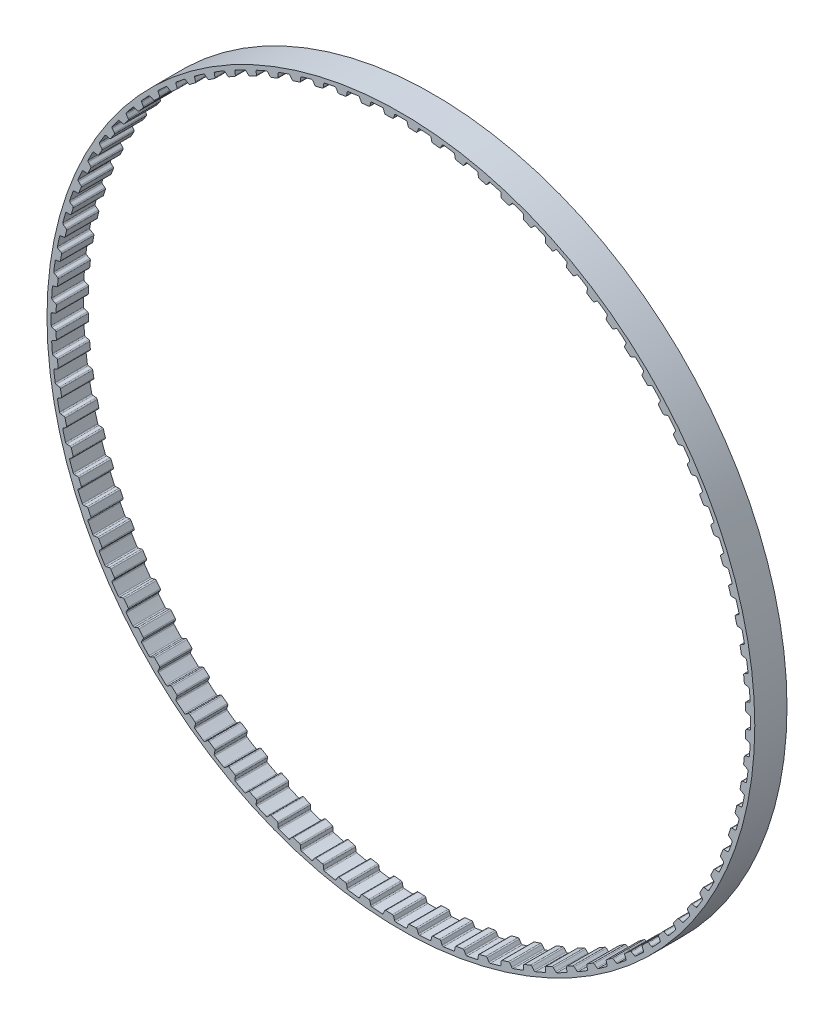
SolidWorks part; units mm, degrees
ref_plane "Front Plane" through (0, 0, 0) normal (0, 0, 1) x (1, 0, 0)
ref_plane "Top Plane" through (0, 0, 0) normal (0, 1, 0) x (1, 0, 0)
ref_plane "Right Plane" through (0, 0, 0) normal (1, 0, 0) x (0, 0, -1)
sketch "Sketch1" plane through (0, 0, 0) normal (0, 0, 1) x (1, 0, 0)
  line L0 (0, 0) -> (-4.6402, 135.8324) construction
  line L1 (0, 0) -> (4.6402, 135.8324) construction
  line L2 (4.6402, 135.8324) -> (-4.6402, 135.8324) construction
  line L3 (4.6402, 135.8324) -> (-4.6402, 135.8324) construction
  circle A0 centre (0, 0) radius 139.4676
  circle A1 centre (0, 0) radius 135.9116
  circle A2 centre (0, 0) radius 137.8166 construction
  dimension "OD" = 278.9352
  dimension "Angle Distance" = 3.913
  dimension "hs" = 3.556
  dimension "ht" = 1.905
extrude "Boss-Extrude1" add sketch "Sketch1" along normal mid plane 12.7
sketch "Sketch2" plane through (0, 0, 0) normal (0, 0, 1) x (1, 0, 0)
  line L1 (0, 139.4676) -> (0, 0) construction
  line L2 (-4.7625, 136.8422) -> (4.7625, 136.8422) construction
  line L4 (-3.0019, 135.8883) -> (-6.2785, 135.7764)
  line L5 (-3.0019, 135.8883) -> (-2.3804, 137.796)
  line L6 (-6.2785, 135.7764) -> (-7.0286, 137.6372)
  line L7 (0, 0) -> (-4.6402, 135.8324) construction
  line L8 (-2.3804, 137.796) -> (-7.0286, 137.6372) construction
  line L9 (2.3804, 137.796) -> (7.0286, 137.6372) construction
  line L10 (6.2785, 135.7764) -> (7.0286, 137.6372)
  line L11 (3.0019, 135.8883) -> (2.3804, 137.796)
  line L12 (3.0019, 135.8883) -> (6.2785, 135.7764)
  line L13 (0, 0) -> (53.3719, 128.8513) construction
  line L14 (-4.7625, 136.8422) -> (-14.2645, 136.18) construction
  line L15 (-9.5135, 136.5111) -> (0, 0) construction
  line L16 (-14.2645, 136.18) -> (-14.1589, 135.1721) construction
  circle A0 centre (0, 0) radius 137.8166 construction
  circle A1 centre (0, 0) radius 137.8166
  circle A2 centre (0, 0) radius 136.8422 construction
  circle A4 centre (0, 0) radius 139.4676 construction
  circle A5 centre (0, 0) radius 135.9116 construction
  point P16 (-2.6912, 136.8422)
  point P20 (0, 136.8422)
  dimension "D1" = 22.5
  dimension "bt" = 4.6482
  dimension "b" = 40
  dimension "Pitch" = 9.525
sketch "Sketch3" plane through (0, 0, 0) normal (0, 0, 1) x (1, 0, 0)
  line L0 (-3.3641, 135.87) -> (3.3641, 135.87)
  line L2 (-3.0019, 135.8883) -> (-2.3804, 137.796) construction
  line L3 (3.0019, 135.8883) -> (2.3804, 137.796) construction
  line L5 (-2.8937, 136.2204) -> (-2.4928, 137.4512)
  line L7 (2.8937, 136.2204) -> (2.4928, 137.4512)
  arc A0 (2.8937, 136.2204) -> (3.3641, 135.87) centre (3.3767, 136.3778) ccw
  circle A1 centre (0, 0) radius 137.8166 construction
  arc A2 (2.0172, 137.8018) -> (-2.0172, 137.8018) centre (0, 0) ccw
  arc A3 (-2.8937, 136.2204) -> (-3.3641, 135.87) centre (-3.3767, 136.3778) cw
  arc A4 (2.4928, 137.4512) -> (2.0172, 137.8018) centre (2.0097, 137.2939) ccw
  arc A5 (-2.4928, 137.4512) -> (-2.0172, 137.8018) centre (-2.0097, 137.2939) cw
  circle A6 centre (0, 0) radius 135.9116 construction
  arc A7 (-3.3641, 135.87) -> (3.3641, 135.87) centre (0, 0) ccw construction
  dimension "ra" = 0.508
  dimension "rr" = 0.508
extrude "Cut-Extrude1" cut sketch "Sketch3" against normal mid plane 12.7
pattern_circular "CirPattern1" count 92 over 360 about axis through (0, 0, 6.35) along (0, 0, -1) of "Cut-Extrude1"
equation "\"D1@Cut-Extrude1\" = \"Width@Boss-Extrude1\""
